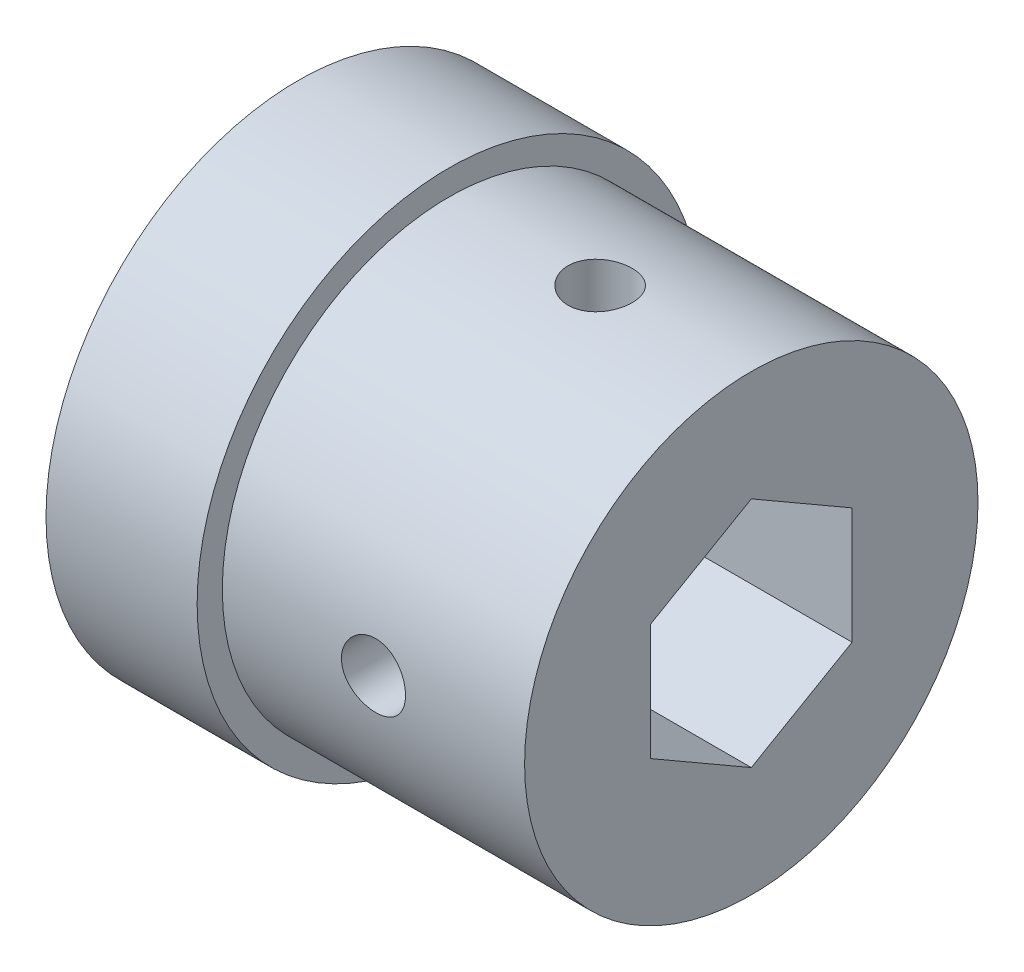
SolidWorks part; units mm, degrees
material "6061-T6 (SS)"
ref_plane "Front Plane" through (0, 0, 0) normal (0, 0, 1) x (1, 0, 0)
ref_plane "Top Plane" through (0, 0, 0) normal (0, 1, 0) x (1, 0, 0)
ref_plane "Right Plane" through (0, 0, 0) normal (1, 0, 0) x (0, 0, -1)
sketch "Sketch1" plane through (0, 0, 0) normal (1, 0, 0) x (0, 0, -1)
  circle A0 centre (0, 0) radius 14.2875
  dimension "D1" = 28.575
extrude "Boss-Extrude1" add sketch "Sketch1" along normal blind 19.05
sketch "Sketch2" plane through (0, 0, 0) normal (-1, 0, 0) x (0, 0, 1)
  circle A0 centre (0, 0) radius 15.875
  dimension "D1" = 31.75
extrude "Boss-Extrude2" add sketch "Sketch2" along normal blind 9.525
sketch "Sketch3" plane through (-9.525, 0, 0) normal (-1, 0, 0) x (0, 0, 1)
  circle A0 centre (0, 0) radius 11.1125
  dimension "D1" = 22.225
sketch "Sketch4" plane through (-9.525, 0, 0) normal (-1, 0, 0) x (0, 0, 1)
  line L1 (0, 7.3323) -> (-6.35, 3.6662)
  line L2 (-6.35, 3.6662) -> (-6.35, -3.6662)
  line L3 (-6.35, -3.6662) -> (0, -7.3323)
  line L4 (0, -7.3323) -> (6.35, -3.6662)
  line L5 (6.35, -3.6662) -> (6.35, 3.6662)
  line L6 (6.35, 3.6662) -> (0, 7.3323)
  circle A0 centre (0, 0) radius 6.35 construction
  dimension "D1" = 12.7
extrude "Cut-Extrude1" cut sketch "Sketch4" against normal through all
sketch "Sketch5" plane through (0, 0, 0) normal (0, 0, 1) x (1, 0, 0)
  circle A0 centre (9.525, 0) radius 2.0193
  dimension "D1" = 4.0386
  dimension "D2" = 9.525
extrude "Cut-Extrude2" cut sketch "Sketch5" against normal through all both and the other way through all
sketch "Sketch6" plane through (0, 0, 0) normal (0, 1, 0) x (1, 0, 0)
  circle A0 centre (9.525, 0) radius 2.0193
  dimension "D1" = 4.0386
  dimension "D2" = 9.525
extrude "Cut-Extrude3" cut sketch "Sketch6" against normal through all both and the other way through all
sketch "Sketch7" plane through (19.05, 0, 0) normal (1, 0, 0) x (0, 0, -1)
  line L0 (4.7625, -7.9375) -> (-4.7625, -7.9375)
  line L1 (7.9375, 4.7625) -> (12.6365, 4.7625)
  line L2 (7.9375, 4.7625) -> (7.9375, -4.7625)
  line L3 (7.9375, -4.7625) -> (12.6365, -4.7625)
  line L4 (12.6365, 4.7625) -> (12.6365, -4.7625)
  line L5 (4.7625, -7.9375) -> (4.7625, -12.6365)
  line L6 (4.7625, -12.6365) -> (-4.7625, -12.6365)
  line L7 (-4.7625, -7.9375) -> (-4.7625, -12.6365)
  line L8 (-7.9375, -4.7625) -> (-7.9375, 4.7625)
  line L9 (-7.9375, -4.7625) -> (-12.6365, -4.7625)
  line L10 (-12.6365, -4.7625) -> (-12.6365, 4.7625)
  line L11 (-7.9375, 4.7625) -> (-12.6365, 4.7625)
  line L12 (-4.7625, 7.9375) -> (4.7625, 7.9375)
  line L13 (-4.7625, 7.9375) -> (-4.7625, 12.6365)
  line L14 (-4.7625, 12.6365) -> (4.7625, 12.6365)
  line L15 (4.7625, 7.9375) -> (4.7625, 12.6365)
  point P4 (12.6365, 0)
  point P21 (0, 0)
  dimension "D1" = 4.699
  dimension "D2" = 9.525
  dimension "D3" = 7.9375
  dimension "D4" = 4
